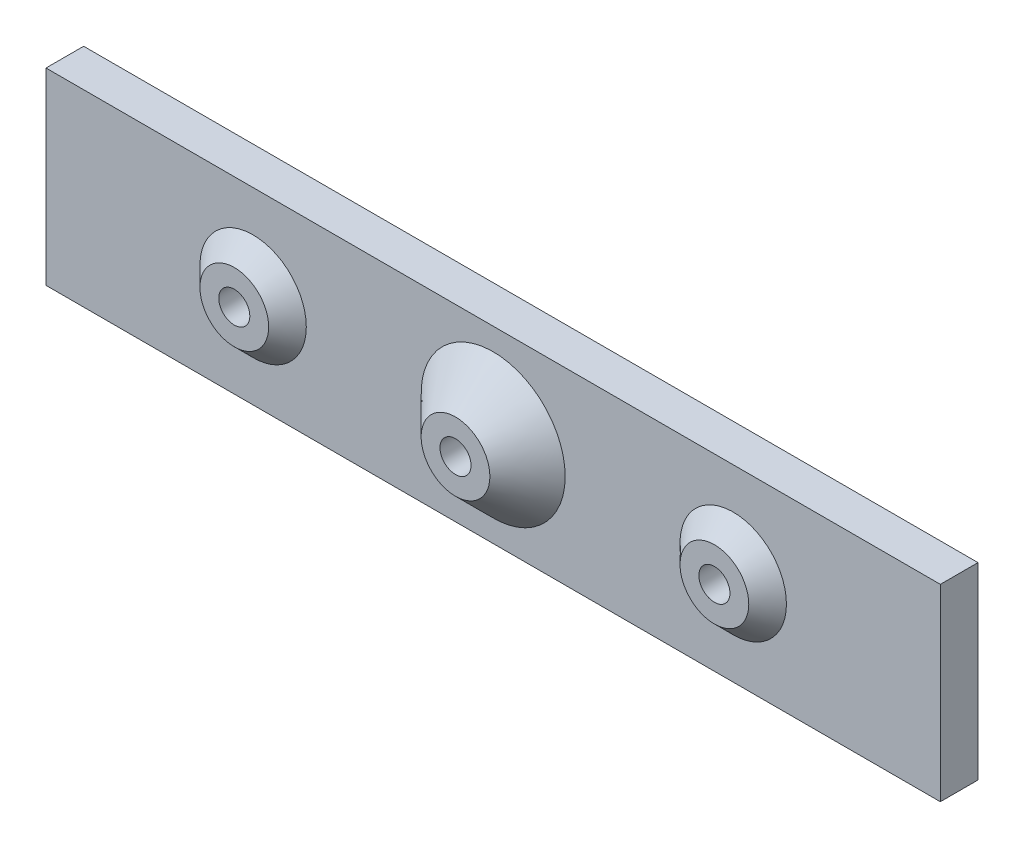
SolidWorks part; units mm, degrees
ref_plane "Front Plane" through (0, 0, 0) normal (0, 0, 1) x (1, 0, 0)
ref_plane "Top Plane" through (0, 0, 0) normal (0, 1, 0) x (1, 0, 0)
ref_plane "Right Plane" through (0, 0, 0) normal (1, 0, 0) x (0, 0, -1)
sketch "Sketch1" plane through (0, 0, 0) normal (0, 0, 1) x (1, 0, 0)
  line L0 (-25.5, 0) -> (25.5, 0) construction
  line L1 (47.5, -10) -> (-47.5, -10)
  line L2 (47.5, -10) -> (47.5, 10)
  line L3 (47.5, 10) -> (-47.5, 10)
  line L4 (-47.5, -10) -> (-47.5, 10)
  line L5 (47.5, -10) -> (-47.5, 10) construction
  line L6 (47.5, 10) -> (-47.5, -10) construction
  circle A0 centre (0, 0) radius 1.65
  circle A1 centre (25.5, 0) radius 1.65
  circle A2 centre (-25.5, 0) radius 1.65
  point P0 (0, 0)
  point P12 (0, 0)
  dimension "D3" = 25.5
  dimension "D4" = 3.3
  dimension "D1" = 20
  dimension "D2" = 95
extrude "Boss-Extrude1" add sketch "Sketch1" along normal blind 4
sketch "Sketch2" plane through (0, 0, 4) normal (0, 0, 1) x (1, 0, 0)
  circle A0 centre (-25.5, 0) radius 1.65
  circle A1 centre (25.5, 0) radius 1.65
extrude "Extrude-Thin1" add sketch "Sketch2" along normal blind 2 thin thin type one direction wall 4
chamfer "Chamfer1" distance 2 angle 45 2 edges at (31.15, 0, 6) (-19.85, 0, 6)
sketch "Sketch3" plane through (0, 0, 4) normal (0, 0, 1) x (1, 0, 0)
  circle A0 centre (0, 0) radius 1.65
extrude "Extrude-Thin2" add sketch "Sketch3" along normal blind 4 thin thin type one direction wall 6
chamfer "Chamfer2" distance 4 angle 45 1 edges at (7.65, 0, 8)
